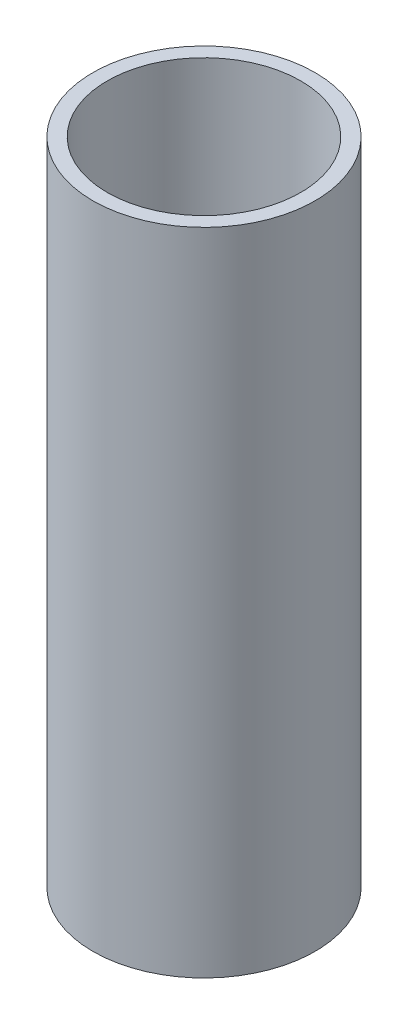
SolidWorks part; units mm, degrees
ref_plane "Front Plane" through (0, 0, 0) normal (0, 0, 1) x (1, 0, 0)
ref_plane "Top Plane" through (0, 0, 0) normal (0, 1, 0) x (1, 0, 0)
ref_plane "Right Plane" through (0, 0, 0) normal (1, 0, 0) x (0, 0, -1)
sketch "Sketch1" plane through (0, 0, 0) normal (0, 1, 0) x (1, 0, 0)
  circle A0 centre (0, 0) radius 55
  dimension "SLEEVE_OD" = 110
extrude "Boss-Extrude1" add sketch "Sketch1" along normal blind 321.8408
sketch "Sketch2" plane through (0, 0, 0) normal (0, 1, 0) x (1, 0, 0)
  circle A0 centre (0, 0) radius 47.8938
  dimension "BORE_D" = 95.7875
extrude "Cut-Extrude1" cut sketch "Sketch2" along normal through all
chamfer "Chamfer1" distance 3.1899 angle 60 rebuild error yes
